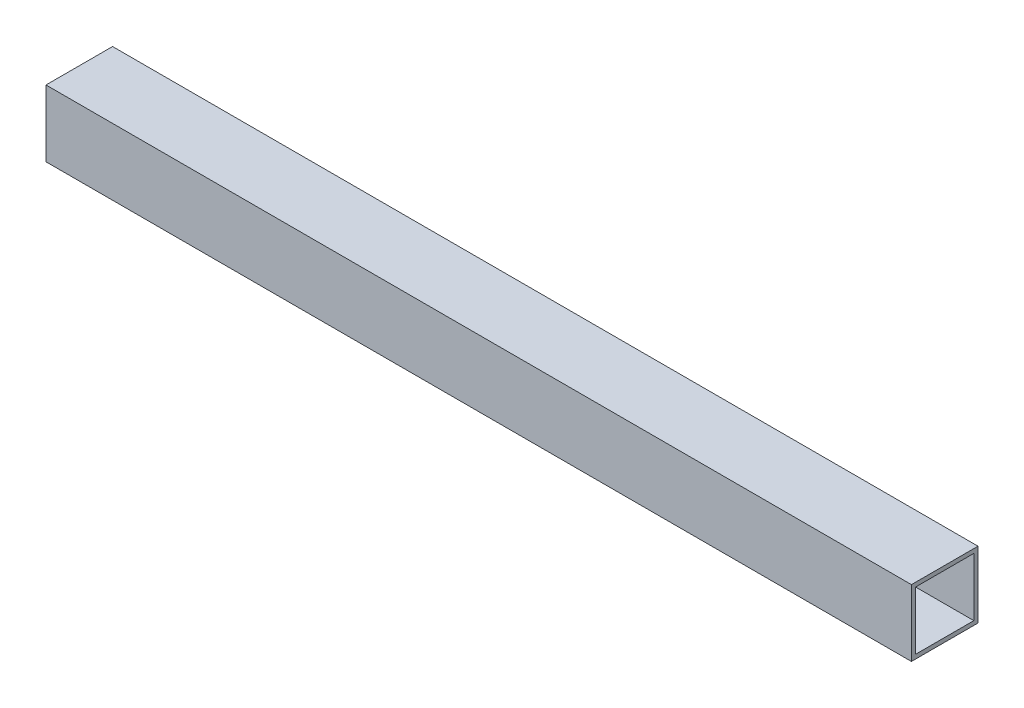
SolidWorks part; units mm, degrees
material "6061-T6 (SS)"
ref_plane "Front" through (0, 0, 0) normal (0, 0, 1) x (1, 0, 0)
ref_plane "Top" through (0, 0, 0) normal (0, 1, 0) x (1, 0, 0)
ref_plane "Right" through (0, 0, 0) normal (1, 0, 0) x (0, 0, -1)
sketch "Sketch1" plane through (0, 0, 0) normal (1, 0, 0) x (0, 0, -1)
  line L1 (12.7, -12.7) -> (-12.7, -12.7)
  line L2 (12.7, -12.7) -> (12.7, 12.7)
  line L3 (12.7, 12.7) -> (-12.7, 12.7)
  line L4 (-12.7, -12.7) -> (-12.7, 12.7)
  line L5 (12.7, -12.7) -> (-12.7, 12.7) construction
  line L6 (12.7, 12.7) -> (-12.7, -12.7) construction
  point P0 (0, 0)
  dimension "D1" = 25.4
extrude "Extrude-Thin1" add sketch "Sketch1" along normal up to surface (330.2 mm away) thin thin type one direction reverse wall 1.5875
